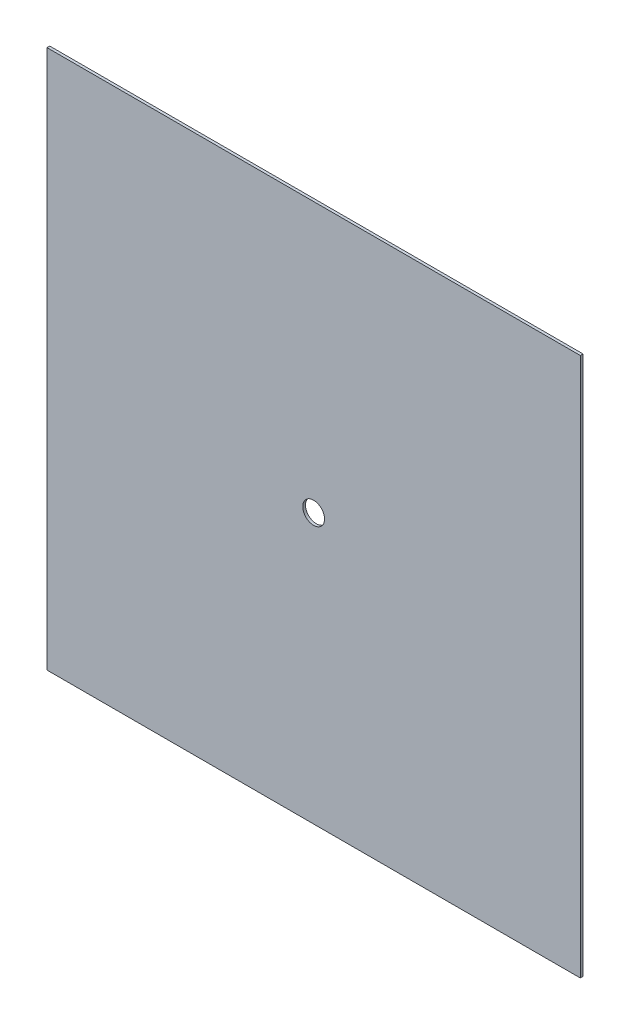
SolidWorks part; units mm, degrees
material "PC High Viscosity"
ref_plane "Front Plane" through (0, 0, 0) normal (0, 0, 1) x (1, 0, 0)
ref_plane "Top Plane" through (0, 0, 0) normal (0, 1, 0) x (1, 0, 0)
ref_plane "Right Plane" through (0, 0, 0) normal (1, 0, 0) x (0, 0, -1)
sketch "Sketch1" plane through (0, 0, 0) normal (0, 0, 1) x (1, 0, 0)
  line L1 (310.8, -314.15) -> (-310.8, -314.15)
  line L2 (310.8, -314.15) -> (310.8, 314.15)
  line L3 (310.8, 314.15) -> (-310.8, 314.15)
  line L4 (-310.8, -314.15) -> (-310.8, 314.15)
  line L5 (310.8, -314.15) -> (-310.8, 314.15) construction
  line L6 (310.8, 314.15) -> (-310.8, -314.15) construction
  point P0 (0, 0)
  dimension "D1" = 621.6
  dimension "D2" = 628.3
extrude "Boss-Extrude1" add sketch "Sketch1" along normal mid plane 3.175
hole_wizard "1 (1) Diameter Hole1" positions "Sketch2" profile "Sketch3" hole size "1" standard "ANSI Inch" end condition up to next
sketch "Sketch2" plane through (0, 0, 1.5875) normal (0, 0, 1) x (1, 0, 0)
  point P0 (0, 0)
  point P3 (0, 0)
  point P4 (0, 0)
sketch "Sketch3" plane through (0, 0, 1.5875) normal (1, 0, 0) x (0, -1, 0)
  line L0 (0, 0) -> (0, 3.175)
  line L1 (0, 3.175) -> (12.7, 3.175)
  line L2 (12.7, 3.175) -> (12.7, 0)
  line L5 (12.7, 0) -> (0, 0)
  line L11 (0, -6.35) -> (0, 107.95) construction
  dimension "Thru Hole Dia." = 25.4
  dimension "Thru Hole Depth" = 3.175
